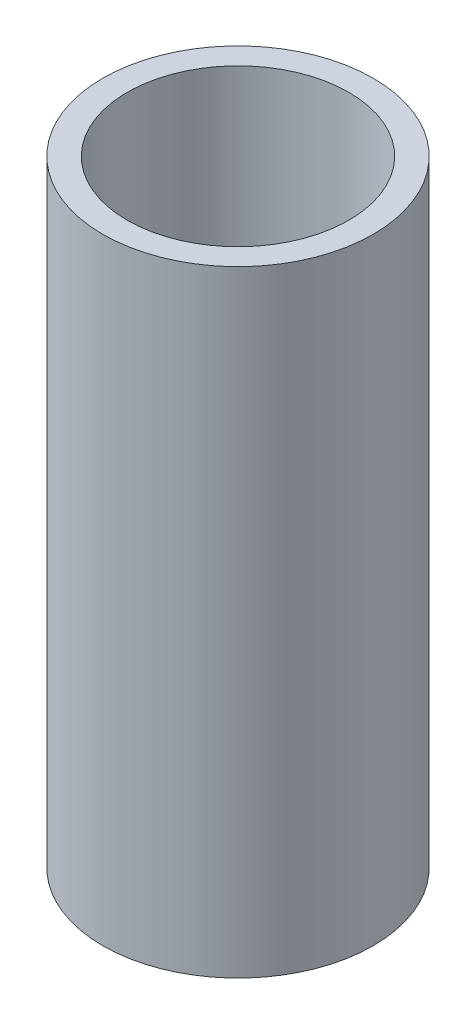
SolidWorks part; units mm, degrees
ref_plane "Front Plane" through (0, 0, 0) normal (0, 0, 1) x (1, 0, 0)
ref_plane "Top Plane" through (0, 0, 0) normal (0, 1, 0) x (1, 0, 0)
ref_plane "Right Plane" through (0, 0, 0) normal (1, 0, 0) x (0, 0, -1)
sketch "Sketch1" plane through (0, 0, 0) normal (0, 1, 0) x (1, 0, 0)
  circle A0 centre (0, 0) radius 17.5
  dimension "SLEEVE_OD" = 35
extrude "Boss-Extrude1" add sketch "Sketch1" along normal blind 79.7501
sketch "Sketch2" plane through (0, 0, 0) normal (0, 1, 0) x (1, 0, 0)
  circle A0 centre (0, 0) radius 14.3443
  dimension "BORE_D" = 28.6886
extrude "Cut-Extrude1" cut sketch "Sketch2" along normal through all
chamfer "Chamfer1" distance 2.838 angle 60 rebuild error yes
